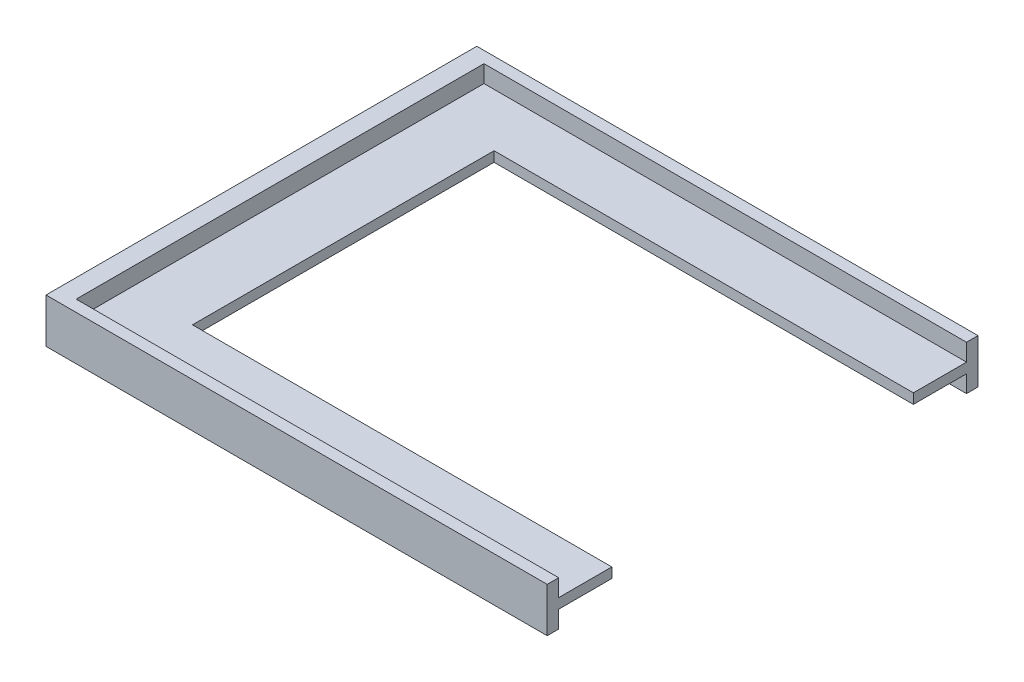
SolidWorks part; units mm, degrees
ref_plane "Front Plane" through (0, 0, 0) normal (0, 0, 1) x (1, 0, 0)
ref_plane "Top Plane" through (0, 0, 0) normal (0, 1, 0) x (1, 0, 0)
ref_plane "Right Plane" through (0, 0, 0) normal (1, 0, 0) x (0, 0, -1)
sketch "Sketch1" plane through (0, 0, 0) normal (0, 1, 0) x (1, 0, 0)
  line L0 (0, 0) -> (5.4, 0)
  line L1 (0, 0) -> (0, -7) construction
  line L2 (5.4, 0) -> (5.4, -7)
  line L3 (0, -7) -> (-53, -7) construction
  line L4 (-53, -7) -> (-53, 0) construction
  line L5 (-53, 0) -> (-58.4, 0) construction
  line L6 (-58.4, 0) -> (-58.4, -7) construction
  line L7 (-58.4, 0) -> (-61.4, 0) construction
  line L8 (-61.4, 0) -> (-61.4, 42) construction
  line L9 (-62.1072, 21) -> (-46.1818, 21) construction
  line L10 (-58.4, -7) -> (-58.4, -9) construction
  line L14 (-58.4, -9) -> (5.4, -9)
  line L20 (-58.4, -7) -> (-53, -7) construction
  line L21 (0, -7) -> (5.4, -7) construction
  line L22 (5.4, -9) -> (5.4, -7)
  line L23 (-58.4, -9) -> (-61.4, -9)
  line L24 (-61.4, -9) -> (-61.4, 0) construction
  line L25 (-53, 0) -> (-53, 42)
  line L26 (0, 0) -> (5.4, -7) construction
  line L27 (0, 42) -> (5.4, 49) construction
  line L28 (-58.4, 49) -> (-53, 42) construction
  line L29 (0, 49) -> (5.4, 49) construction
  line L30 (-58.4, 49) -> (-53, 49) construction
  line L31 (-58.4, 49) -> (-58.4, 51) construction
  line L32 (-58.4, 42) -> (-58.4, 49) construction
  line L33 (-61.4, 51) -> (-61.4, 42) construction
  line L34 (-58.4, 51) -> (-61.4, 51)
  line L35 (5.4, 51) -> (5.4, 49)
  line L36 (-58.4, 51) -> (5.4, 51)
  line L37 (-58.4, 42) -> (-61.4, 42) construction
  line L38 (-53, 42) -> (-58.4, 42) construction
  line L39 (-53, 49) -> (-53, 42) construction
  line L40 (0, 49) -> (-53, 49) construction
  line L41 (5.4, 42) -> (5.4, 49)
  line L42 (0, 42) -> (0, 49) construction
  line L43 (0, 42) -> (5.4, 42)
  line L44 (-61.4, -9) -> (-64.4, -9)
  line L45 (-64.4, -9) -> (-64.4, 51)
  line L46 (-64.4, 51) -> (-61.4, 51)
  line L47 (-53, 42) -> (0, 42)
  line L48 (0, 0) -> (-53, 0)
  point P14 (-61.4, 21)
  point P24 (-61.4, 21)
  dimension "D3" = 2
  dimension "D4" = 5.4
  dimension "D5" = 53
  dimension "D6" = 5.4
  dimension "D7" = 7
  dimension "D8" = 3
  dimension "D9" = 3
  dimension "D10" = 60
  dimension "D11" = 42
extrude "Boss-Extrude1" add sketch "Sketch1" along normal blind 1.4
sketch "Sketch2" plane through (0, 1.4, 0) normal (0, 1, 0) x (1, 0, 0)
  line L0 (5.4, 42) -> (5.4, 51) construction
  line L1 (-61.4, 35.4314) -> (-61.8, 35.4314) construction
  line L2 (-53, -7) -> (-53, -7.4) construction
  line L3 (-64.4, 51) -> (5.4, 51)
  line L5 (-53, 49) -> (-53, 49.4) construction
  line L6 (-64.4, 51) -> (-64.4, -9)
  line L11 (-61.8, 49.4) -> (5.4, 49.4)
  line L12 (5.4, 51) -> (5.4, 49.4)
  line L14 (5.4, -9) -> (5.4, 0) construction
  line L15 (-64.4, -9) -> (5.4, -9)
  line L17 (-61.8, -7.4) -> (5.4, -7.4)
  line L18 (5.4, -9) -> (5.4, -7.4)
  line L21 (-61.8, 49.4) -> (-61.8, -7.4)
  dimension "D1" = 1.6
extrude "Boss-Extrude2" add sketch "Sketch2" along normal blind 2.4 and the other way blind 3.8
